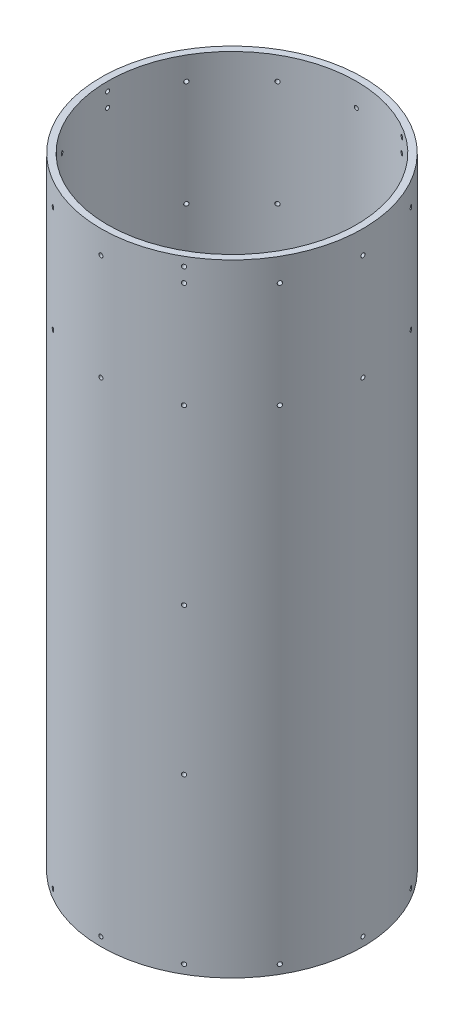
SolidWorks part; units mm, degrees
material "PVC Rigid"
ref_plane "Front Plane" through (0, 0, 0) normal (0, 0, 1) x (1, 0, 0)
ref_plane "Top Plane" through (0, 0, 0) normal (0, 1, 0) x (1, 0, 0)
ref_plane "Right Plane" through (0, 0, 0) normal (1, 0, 0) x (0, 0, -1)
sketch "Sketch1" plane through (0, 0, 0) normal (0, 1, 0) x (1, 0, 0)
  circle A0 centre (0, 0) radius 93.6625
  circle A1 centre (0, 0) radius 88.9
  dimension "D1" = 187.325
  dimension "D2" = 177.8
extrude "Boss-Extrude1" add sketch "Sketch1" along normal mid plane 444.5
ref_plane "Plane1" through (-93.6625, 0, 0) normal (-1, 0, 0) x (0, 0, 1)
sketch "Sketch3" plane through (-93.6625, 0, 0) normal (-1, 0, 0) x (0, 0, 1)
  line L0 (0, -103.0288) -> (0, 103.0288) construction
  line L1 (-88.9, -222.25) -> (88.9, -222.25) construction
  circle A0 centre (0, -215.9) radius 1.4351
  dimension "D1" = 2.8702
  dimension "D2" = 6.35
extrude "Cut-Extrude1" cut sketch "Sketch3" against normal blind 21.59
pattern_circular "CirPattern1" count 12 over 360 about axis through (0, 222.25, 0) along (0, -1, 0) of "Cut-Extrude1" reverse direction yes
sketch "Sketch4" plane through (-93.6625, 0, 0) normal (-1, 0, 0) x (0, 0, 1)
  line L0 (0, -103.0288) -> (0, 103.0288) construction
  line L1 (93.6625, 222.25) -> (-93.6625, 222.25) construction
  circle A0 centre (0, 215.9) radius 1.4351
  dimension "D1" = 2.8702
  dimension "D2" = 6.35
extrude "Cut-Extrude2" cut sketch "Sketch4" against normal blind 34.798
pattern_circular "CirPattern2" count 3 over 360 about axis through (0, 222.25, 0) along (0, -1, 0) of "Cut-Extrude2" reverse direction yes
sketch "Sketch9" plane through (-93.6625, 0, 0) normal (-1, 0, 0) x (0, 0, 1)
  line L0 (0, -103.0288) -> (0, 103.0288) construction
  circle A0 centre (0, 130.048) radius 1.4351
  circle A1 centre (0, 215.9) radius 1.4351 construction
  dimension "D1" = 85.852
  dimension "D2" = 2.8702
extrude "Cut-Extrude4" cut sketch "Sketch9" against normal blind 15.24
pattern_circular "CirPattern4" count 12 over 360 about axis through (0, 222.25, 0) along (0, -1, 0) of "Cut-Extrude4"
sketch "Sketch7" plane through (-93.6625, 0, 0) normal (-1, 0, 0) x (0, 0, 1)
  line L0 (0, -103.0288) -> (0, 103.0288) construction
  circle A0 centre (0, 6.35) radius 1.4351
  circle A1 centre (0, -98.552) radius 1.4351
  circle A4 centre (0, 130.048) radius 1.4351 construction
  circle A5 centre (0, -215.9) radius 1.4351 construction
  dimension "D1" = 123.698
  dimension "D2" = 117.348
  dimension "D3" = 2.8702
  dimension "D4" = 2.8702
extrude "Cut-Extrude3" cut sketch "Sketch7" against normal blind 15.24
pattern_circular "CirPattern3" count 3 over 360 about axis through (0, 222.25, 0) along (0, -1, 0) of "Cut-Extrude3" reverse direction yes
sketch "Sketch10" plane through (-93.6625, 0, 0) normal (-1, 0, 0) x (0, 0, 1)
  line L0 (0, -103.0288) -> (0, 103.0288) construction
  circle A0 centre (0, 205.74) radius 1.4351
  circle A1 centre (0, 215.9) radius 1.4351 construction
  dimension "D1" = 10.16
  dimension "D2" = 2.8702
extrude "Cut-Extrude5" cut sketch "Sketch10" against normal blind 21.082
pattern_circular "CirPattern5" count 12 over 360 about axis through (0, 222.25, 0) along (0, -1, 0) of "Cut-Extrude5"
